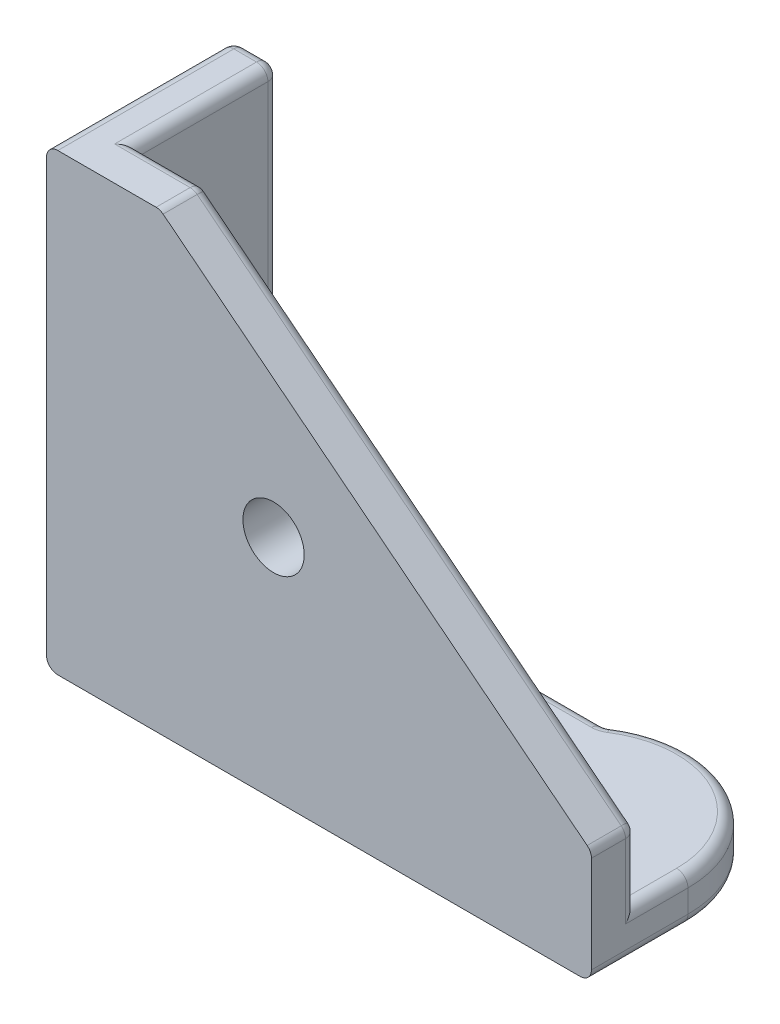
SolidWorks part; units mm, degrees
material "ABS"
ref_plane "Front Plane" through (0, 0, 0) normal (0, 0, 1) x (1, 0, 0)
ref_plane "Top Plane" through (0, 0, 0) normal (0, 1, 0) x (1, 0, 0)
ref_plane "Right Plane" through (0, 0, 0) normal (1, 0, 0) x (0, 0, -1)
sketch "Sketch1" plane through (0, 0, 0) normal (0, 0, 1) x (1, 0, 0)
  line L0 (0, 40) -> (0, 0)
  line L1 (0, 0) -> (48, 0)
  line L2 (48, 0) -> (48, 10)
  line L3 (48, 10) -> (10, 40)
  line L4 (10, 40) -> (0, 40)
  dimension "D1" = 48
  dimension "D2" = 40
  dimension "D3" = 10
  dimension "D4" = 10
extrude "Boss-Extrude1" add sketch "Sketch1" along normal blind 4
sketch "Sketch2" plane through (0, 0, 0) normal (0, 0, -1) x (-1, 0, 0)
  line L0 (0, 0) -> (-48, 0) construction
  line L1 (-48, 0) -> (-48, 10) construction
  line L2 (0, 40) -> (0, 0) construction
  line L3 (-10, 40) -> (0, 40) construction
  line L4 (0, 0) -> (-48, 0)
  line L5 (-48, 0) -> (-48, 4)
  line L6 (0, 40) -> (0, 0)
  line L7 (-4, 40) -> (0, 40)
  line L8 (-48, 4) -> (-4, 4)
  line L9 (-4, 4) -> (-4, 40)
  dimension "D1" = 4
  dimension "D2" = 4
extrude "Boss-Extrude2" add sketch "Sketch2" along normal blind 12.5
sketch "Sketch4" plane through (0, 0, 0) normal (-1, 0, 0) x (0, 0, 1)
  line L0 (-2.5, 40) -> (-2.5, 0) construction
  line L1 (4, 40) -> (-12.5, 40) construction
  line L2 (4, 0) -> (-12.5, 0) construction
  line L3 (-12.5, 0) -> (-12.5, 40) construction
  circle A0 centre (-2.5, 31) radius 2.7
  circle A1 centre (-2.5, 13) radius 2.7
  dimension "D2" = 5.4
  dimension "D3" = 5.4
  dimension "D5" = 18
  dimension "D1" = 10
  dimension "D4" = 13
extrude "Cut-Extrude1" cut sketch "Sketch4" against normal up to surface (4 mm away) up to face at (4, 26.5, -7.8125)
sketch "Sketch5" plane through (4, 0, 0) normal (1, 0, 0) x (0, 0, -1)
  circle A0 centre (2.5, 31) radius 4.75
  circle A1 centre (2.5, 13) radius 4.75
  dimension "D1" = 9.5
  dimension "D2" = 9.5
extrude "Cut-Extrude2" cut sketch "Sketch5" along normal blind 8
chamfer "Chamfer1" distance 2.5 angle 35 2 edges at (12, 13, 0) (12, 31, 0) first distance on face at (12, 13, 1.125) first distance on face at (12, 31, 1.125)
fillet "Fillet1" radius 1 8 edges at (8.8753, 8.9611, 0) (8.8753, 17.0389, 0) (8.8753, 26.9611, 0) (8.8753, 35.0389, 0) (13.7505, 13, 0) (12.1751, 13, 2.25) (13.7505, 31, 0) (12.1751, 31, 2.25)
sketch "Sketch6" plane through (0, 0, 0) normal (0, -1, 0) x (1, 0, 0)
  line L0 (0, 4) -> (0, -12.5) construction
  line L1 (48, -12.5) -> (0, -12.5) construction
  circle A0 centre (38.3, -4.5) radius 2.25
  dimension "D1" = 4.5
  dimension "D3" = 8
  dimension "D2" = 38.3
sketch "Sketch8" plane through (0, 0, 0) normal (0, -1, 0) x (1, 0, 0)
  line L0 (48, -12.5) -> (0, -12.5) construction
  line L1 (48, -12.5) -> (32.8146, -12.5)
  line L2 (48, -12.5) -> (48, -4.5)
  arc A0 (32.8146, -12.5) -> (48, -4.5) centre (38.3, -4.5) ccw
  line M2 (0, -12.5) -> (48, -12.5)
  line M3 (48, -12.5) -> (48, 4)
extrude "Boss-Extrude3" add sketch "Sketch8" against normal up to surface (4 mm away) contours A0 M2 region at (38.3, 0, -13.1854) up to face at (20.5, 4, -7.8125)
extrude "Cut-Extrude3" cut sketch "Sketch8<3>" against normal up to surface (4 mm away) contours A0 L1 M3 region at (46.8023, 0, -10.5972) up to face at (26.4333, 4, -9.6583)
sketch "Sketch8<3>" plane through (0, 0, 0) normal (0, -1, 0) x (1, 0, 0) same geometry as "Sketch8"
extrude "Cut-Extrude4" cut sketch "Sketch6" against normal up to surface (4 mm away) up to face at (23.4457, 4, -7.2664)
fillet "Fillet2" radius 1 18 edges at (48, 0, -0.25) (42.8211, 0, -13.0819) (4, 22, -12.5) (2, 40, -12.5) (0, 20, -12.5) (16.4073, 0, -12.5) (32.8146, 2, -12.5) (18.4073, 4, -12.5) (0, 0, -4.25) (48, 10, 2) (29, 25, 0) (10, 40, 2) (0, 40, -4.25) (42.8211, 4, -13.0819)
sketch "Sketch9" plane through (0, 0, 4) normal (0, 0, 1) x (1, 0, 0)
  line L0 (0, 39) -> (0, 1) construction
  line L1 (1, 0) -> (47, 0) construction
  circle A0 centre (20, 20) radius 2.7
  dimension "D1" = 20
  dimension "D3" = 5.4
  dimension "D2" = 20
extrude "Cut-Extrude5" cut sketch "Sketch9" against normal up to surface (4 mm away) up to face at (12.6571, 21.7015, 0)
